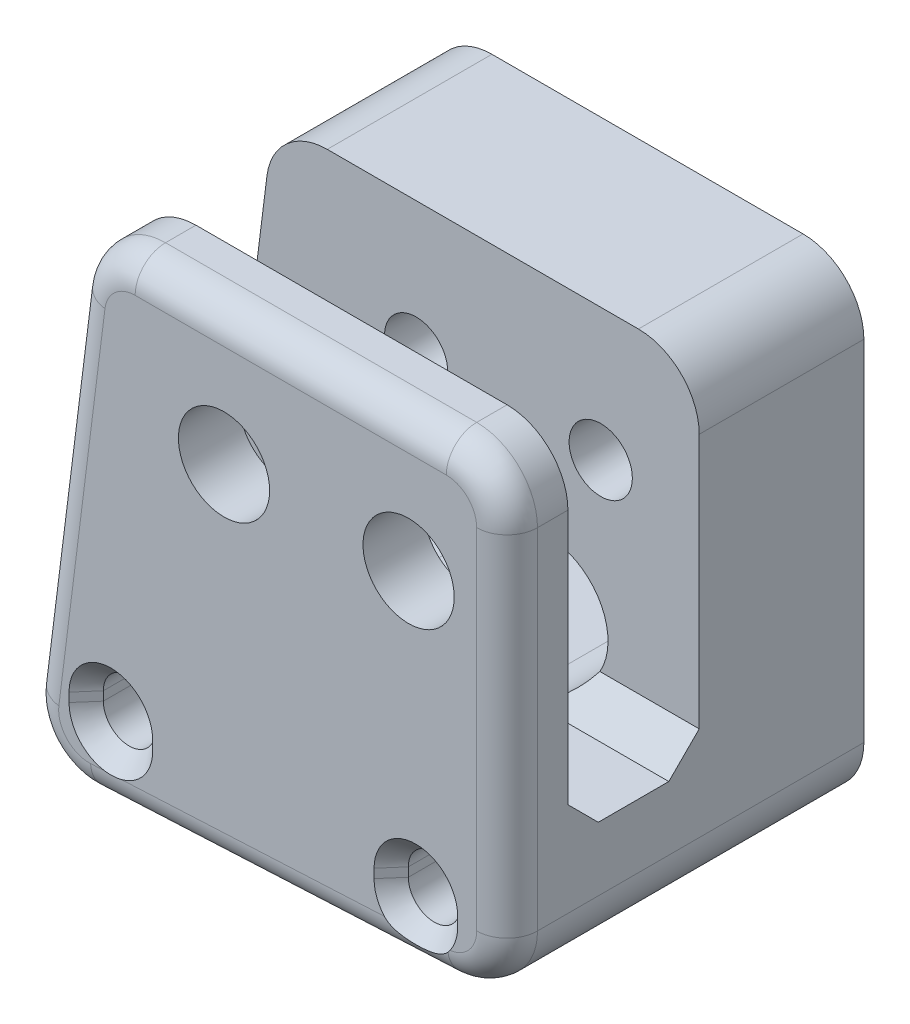
SolidWorks part; units mm, degrees
material "PET"
ref_plane "Front Plane" through (0, 0, 0) normal (0, 0, 1) x (1, 0, 0)
ref_plane "Top Plane" through (0, 0, 0) normal (0, 1, 0) x (1, 0, 0)
ref_plane "Right Plane" through (0, 0, 0) normal (1, 0, 0) x (0, 0, -1)
sketch "Sketch1" plane through (0, 0, 0) normal (0, 0, 1) x (1, 0, 0)
  line L0 (9.9949, 9.271) -> (9.9949, -24.688) construction
  line L1 (22.6995, -24.0574) -> (-66.4095, -28.4803) construction
  line L2 (9.9949, 9.271) -> (9.9949, -15.163)
  line L3 (9.9949, 9.271) -> (-12.2301, 9.271)
  line L4 (-12.2301, 9.271) -> (-15.4575, -16.4263)
  line L5 (-15.4575, -16.4263) -> (9.9949, -15.163)
  dimension "D1" = 9.525
  dimension "D2" = 80
  dimension "D3" = 22.225
extrude "Boss-Extrude1" add sketch "Sketch1" along normal blind 3.175
extrude "Boss-Extrude2" add sketch "Sketch1<2>" against normal up to surface (8.5979 mm away) from offset 6.858 separate body offset against normal yes
sketch "Sketch1<2>" plane through (0, 0, 0) normal (0, 0, 1) x (1, 0, 0) same geometry as "Sketch1"
sketch "Sketch3" plane through (0, 0, -6.858) normal (0, 0, 1) x (1, 0, 0)
  line L0 (9.9949, 9.271) -> (9.9949, -15.163) construction
  line L1 (-15.4575, -16.4263) -> (-12.2301, 9.271) construction
  line L2 (9.9949, -15.163) -> (-15.4575, -16.4263) construction
  line L3 (9.9949, -8.813) -> (9.9949, -15.163)
  line L4 (-15.4575, -16.4263) -> (-14.5013, -8.813)
  line L5 (9.9949, -15.163) -> (-15.4575, -16.4263)
  line L6 (9.9949, -8.813) -> (-14.5013, -8.813)
  dimension "D1" = 6.35
extrude "Boss-Extrude3" add sketch "Sketch3" along normal up to surface (6.858 mm away) up to face at (-1.9245, -3.2618, 0)
hole_wizard "CSK SLOT for #2 Flat Head Machine Screw1" positions "Sketch4" profile "Sketch5" size "#2" standard "ANSI Inch" slot yes end condition through all
sketch "Sketch4" plane through (0, 0, 3.175) normal (0, 0, 1) x (1, 0, 0)
  line L0 (5.2324, -13.808) -> (5.2324, -10.633) construction
  line L1 (9.9949, -15.163) -> (9.9949, 9.271) construction
  line L2 (-15.4575, -16.4263) -> (9.9949, -15.163) construction
  point P0 (5.2324, -12.2205)
  point P2 (-10.695, -12.2205)
  dimension "D1" = 3.175
  dimension "D2" = 3.175
  dimension "D3" = 4.7625
  dimension "D4" = 4.7625
sketch "Sketch5" plane through (5.2324, -12.2205, 3.175) normal (1, 0, 0) x (0, -1, 0)
  line L0 (0, 0) -> (0, 18.6309)
  line L1 (0, 18.6309) -> (1.3525, 18.6309)
  line L2 (1.3525, 18.6309) -> (1.3525, 0.9569)
  line L3 (1.3525, 0.9569) -> (2.1844, 0)
  line L5 (2.1844, 0) -> (0, 0)
  line L6 (-1.3525, 0.9569) -> (-2.1844, 0) construction
  line L11 (0, -6.35) -> (0, 107.95) construction
  dimension "Thru Hole Dia." = 2.7051
  dimension "Thru Hole Depth" = 18.6309
  dimension "Near C'Sink Dia." = 4.3688
  dimension "Near C'Sink Angle" = 82
fillet "Fillet1" radius 3.175 6 edges at (-12.2301, 9.271, -11.157) (-12.2301, 9.271, 1.5875) (9.9949, 9.271, 1.5875) (9.9949, 9.271, -11.157) (9.9949, -15.163, -6.1405) (-15.4575, -16.4263, -6.1405)
chamfer "Chamfer1" distance 1.5875 angle 45 2 edges at (-2.2532, -8.813, 0) (-2.2532, -8.813, -6.858)
hole_wizard "3/16 (0.1875) Diameter Hole1" positions "Sketch6" profile "Sketch7" hole size "3/16" standard "ANSI Inch" end condition up to next
sketch "Sketch6" plane through (0, 0, 3.175) normal (0, 0, 1) x (1, 0, 0)
  point P0 (4.8514, 2.3622)
  point P3 (-4.7879, 2.3622)
sketch "Sketch7" plane through (4.8514, 2.3622, 3.175) normal (1, 0, 0) x (0, -1, 0)
  line L0 (0, 0) -> (0, 3.175)
  line L1 (0, 3.175) -> (2.3812, 3.175)
  line L2 (2.3812, 3.175) -> (2.3812, 0)
  line L5 (2.3812, 0) -> (0, 0)
  line L11 (0, -6.35) -> (0, 107.95) construction
  dimension "Thru Hole Dia." = 4.7625
  dimension "Thru Hole Depth" = 3.175
hole_wizard "#0 Clearance Hole1" positions "Sketch8" profile "Sketch9" hole size "#0" standard "ANSI Inch" end condition up to next
sketch "Sketch8" plane through (0, 0, -15.4559) normal (0, 0, -1) x (-1, 0, 0)
  circle A0 centre (4.7879, 2.3622) radius 2.3812 construction
  circle A1 centre (-4.8514, 2.3622) radius 2.3812 construction
  point P0 (-4.8514, 2.3622)
  point P2 (4.7879, 2.3622)
sketch "Sketch9" plane through (4.8514, 2.3622, -15.4559) normal (1, 0, 0) x (0, 1, 0)
  line L0 (0, 0) -> (0, 8.5979)
  line L1 (0, 8.5979) -> (0.9271, 8.5979)
  line L2 (0.9271, 8.5979) -> (0.9271, 0)
  line L5 (0.9271, 0) -> (0, 0)
  line L11 (0, -6.35) -> (0, 107.95) construction
  dimension "Thru Hole Dia." = 1.8542
  dimension "Thru Hole Depth" = 8.5979
hole_wizard "Hole1" positions "Sketch10" profile "Sketch11" legacy
sketch "Sketch10" plane through (0, 0, -6.858) normal (0, 0, 1) x (1, 0, 0)
  point P0 (4.8514, 2.3622)
  point P3 (-4.7879, 2.3622)
sketch "Sketch11" plane through (4.8514, 2.3622, -6.858) normal (1, 0, 0) x (0, -1, 0)
  line L0 (0, 0) -> (0, 3.048)
  line L1 (0, 3.048) -> (1.524, 3.048)
  line L2 (1.524, 3.048) -> (1.651, 0)
  line L3 (1.651, 0) -> (0, 0)
  line L4 (0, 110) -> (0, -10) construction
  dimension "Minor Diameter" = 3.048
  dimension "Depth" = 3.048
  dimension "Major Diameter" = 3.302
sketch "Sketch13" plane through (0, 0, -15.4559) normal (0, 0, -1) x (-1, 0, 0)
  line L0 (-2.0574, -5.638) -> (6.1277, -5.638) construction
  line L1 (-2.0574, -2.463) -> (6.1277, -2.463)
  line L2 (-2.0574, -8.813) -> (6.1277, -8.813)
  line L3 (14.986, -12.672) -> (12.5792, 6.4917) construction
  line L4 (-9.9949, 6.096) -> (-9.9949, -12.1417) construction
  line L5 (14.5013, -8.813) -> (-9.9949, -8.813) construction
  arc A0 (-2.0574, -2.463) -> (-2.0574, -8.813) centre (-2.0574, -5.638) ccw
  arc A1 (6.1277, -8.813) -> (6.1277, -2.463) centre (6.1277, -5.638) ccw
  point P2 (2.0351, -5.638)
  point P7 (-5.2324, -5.638)
  point P8 (9.3027, -5.638)
  dimension "D1" = 4.7625
  dimension "D2" = 4.7625
  dimension "D3" = 6.35
extrude "Cut-Extrude2" cut sketch "Sketch13" against normal up to next
fillet "Fillet3" radius 1.5875 8 edges at (9.1199, -14.3304, 3.175) (-2.3505, -15.7758, 3.175) (-14.1638, -15.2266, 3.175) (-13.7826, -3.0902, 3.175) (-11.5294, 8.4768, 3.175) (-1.3045, 9.271, 3.175) (9.065, 8.3411, 3.175) (9.9949, -3.0228, 3.175)
